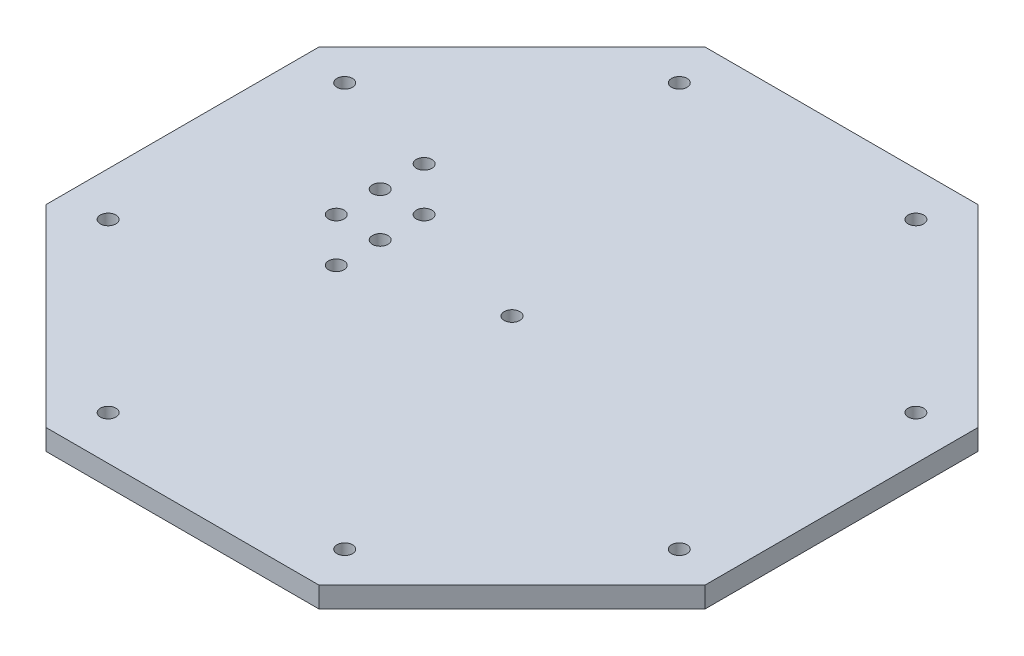
SolidWorks part; units mm, degrees
material "Custom Plastic"
ref_plane "Front Plane" through (0, 0, 0) normal (0, 0, 1) x (1, 0, 0)
ref_plane "Top Plane" through (0, 0, 0) normal (0, 1, 0) x (1, 0, 0)
ref_plane "Right Plane" through (0, 0, 0) normal (1, 0, 0) x (0, 0, -1)
ref_axis "Axis1" through (0, 6.2941, 0) along (0, -1, 0)
sketch "Sketch1" plane through (0, 0, 0) normal (0, 1, 0) x (1, 0, 0)
  line L1 (-39.4538, 95.25) -> (-95.25, 39.4538)
  line L2 (-95.25, 39.4538) -> (-95.25, -39.4538)
  line L3 (-95.25, -39.4538) -> (-39.4538, -95.25)
  line L4 (-39.4538, -95.25) -> (39.4538, -95.25)
  line L5 (39.4538, -95.25) -> (95.25, -39.4538)
  line L6 (95.25, -39.4538) -> (95.25, 39.4538)
  line L7 (95.25, 39.4538) -> (39.4538, 95.25)
  line L8 (39.4538, 95.25) -> (-39.4538, 95.25)
  circle A0 centre (0, 0) radius 95.25 construction
  dimension "D1" = 190.5
extrude "Base" add sketch "Sketch1" along normal blind 5.9944
sketch "Sketch2" plane through (0, 5.9944, 0) normal (0, 1, 0) x (1, 0, 0)
  line L0 (39.4538, 95.25) -> (-39.4538, 95.25) construction
  line L1 (34.1933, 82.55) -> (-34.1933, 82.55)
  line L2 (-34.1933, 82.55) -> (-82.55, 34.1933)
  line L3 (-82.55, 34.1933) -> (-82.55, -34.1933)
  line L4 (-82.55, -34.1933) -> (-34.1933, -82.55)
  line L5 (-34.1933, -82.55) -> (34.1933, -82.55)
  line L6 (34.1933, -82.55) -> (82.55, -34.1933)
  line L7 (82.55, -34.1933) -> (82.55, 34.1933)
  line L8 (82.55, 34.1933) -> (34.1933, 82.55)
  circle A0 centre (0, 0) radius 82.55 construction
  dimension "D1" = 12.7
hole_wizard "Mounting holes" positions "Sketch4" profile "Sketch3" hole size "#8" standard "ANSI Inch"
sketch "Sketch4" plane through (0, 5.9944, 0) normal (0, 1, 0) x (1, 0, 0)
  point P0 (-34.1933, 82.55)
  point P8 (34.1933, 82.55)
  point P11 (82.55, 34.1933)
  point P14 (82.55, -34.1933)
  point P17 (34.1933, -82.55)
  point P20 (-34.1933, -82.55)
  point P23 (-82.55, -34.1933)
  point P26 (-82.55, 34.1933)
sketch "Sketch3" plane through (-34.1933, 5.9944, -82.55) normal (1, 0, 0) x (0, 0, 1)
  line L0 (0, 0) -> (0, 5.9944)
  line L1 (0, 5.9944) -> (2.2479, 5.9944)
  line L2 (2.2479, 5.9944) -> (2.2479, 0)
  line L5 (2.2479, 0) -> (0, 0)
  line L10 (0, 5.9944) -> (-2.2479, 5.9944) construction
  line L11 (0, -6.35) -> (0, 107.95) construction
  dimension "Hole Dia." = 4.4958
  dimension "Hole Depth" = 5.9944
  dimension "Drill Angle" = 180
sketch "Sketch5" plane through (0, 5.9944, 0) normal (0, 1, 0) x (1, 0, 0)
  line L0 (0, 0) -> (-95.25, 0) construction
  line L1 (-95.25, 39.4538) -> (-95.25, -39.4538) construction
  line L2 (-50.8, 0) -> (-50.8, 25.4) construction
  point P4 (-12.7, 0)
  point P5 (-25.4, 0)
  point P7 (-38.1, 0)
  point P8 (-50.8, 0)
  point P11 (-50.8, 12.7)
  point P12 (-38.1, 12.7)
  point P14 (-38.1, -12.7)
  dimension "D1" = 12.7
  dimension "D2" = 12.7
  dimension "D3" = 12.7
  dimension "D4" = 12.7
  dimension "D5" = 25.4
  dimension "D6" = 12.7
hole_wizard "#8 Clearance Hole1" positions "Sketch7" profile "Sketch6" hole size "#8" standard "ANSI Inch" end condition through all
sketch "Sketch7" plane through (0, 5.9944, 0) normal (0, 1, 0) x (1, 0, 0)
  point P0 (0, 0)
  point P9 (-38.1, 0)
  point P12 (-50.8, 0)
  point P15 (-50.8, 12.7)
  point P18 (-50.8, 25.4)
  point P22 (-38.1, 12.7)
  point P25 (-38.1, -12.7)
sketch "Sketch6" plane through (0, 5.9944, 0) normal (1, 0, 0) x (0, 0, 1)
  line L0 (0, 0) -> (0, 5.9944)
  line L1 (0, 5.9944) -> (2.2479, 5.9944)
  line L2 (2.2479, 5.9944) -> (2.2479, 0)
  line L5 (2.2479, 0) -> (0, 0)
  line L11 (0, -6.35) -> (0, 107.95) construction
  dimension "Thru Hole Dia." = 4.4958
  dimension "Thru Hole Depth" = 5.9944
equation "\"MAT_THICKNESS\"=0.236"
equation "\"D1@Base\"=\"MAT_THICKNESS\""
